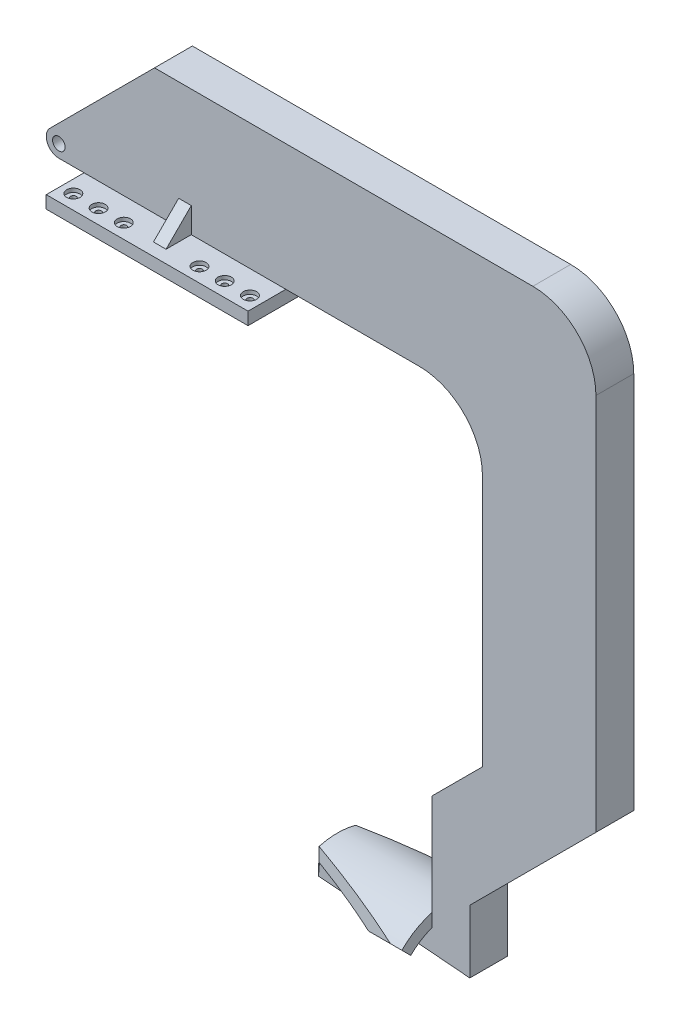
SolidWorks part; units mm, degrees
material "Stainless Steel (ferritic)"
ref_plane "Front Plane" through (0, 0, 0) normal (0, 0, 1) x (1, 0, 0)
ref_plane "Top Plane" through (0, 0, 0) normal (0, 1, 0) x (1, 0, 0)
ref_plane "Right Plane" through (0, 0, 0) normal (1, 0, 0) x (0, 0, -1)
sketch "Sketch1" plane through (0, 0, 0) normal (0, 0, 1) x (1, 0, 0)
  line L0 (-7.0711, 7.0711) -> (75.8579, 90)
  line L1 (75.8579, 90) -> (375.8579, 90)
  line L2 (425.8579, 40) -> (425.8579, -260)
  line L3 (425.8579, -260) -> (325.8579, -360)
  line L4 (325.8579, -360) -> (325.8579, -410)
  line L5 (325.8579, -410) -> (205.8579, -400)
  line L6 (205.8579, -400) -> (205.8579, -380)
  line L7 (205.8579, -380) -> (295.8579, -380)
  line L8 (295.8579, -380) -> (295.8579, -40) construction
  line L9 (285.8579, -10) -> (0, -10)
  line L10 (295.8579, -300) -> (335.8579, -260)
  line L11 (335.8579, -260) -> (335.8579, -60)
  line L12 (295.8579, -300) -> (295.8579, -380)
  arc A0 (295.8579, -40) -> (285.8579, -10) centre (245.8579, -40) ccw construction
  arc A1 (375.8579, 90) -> (425.8579, 40) centre (375.8579, 40) cw
  arc A2 (-7.0711, 7.0711) -> (0, -10) centre (0, 0) ccw
  circle A3 centre (0, 0) radius 5
  arc A4 (285.8579, -10) -> (335.8579, -60) centre (285.8579, -60) cw
  point P17 (325.8579, -260)
  point P18 (0, 0)
  point P19 (0, 0)
  point P24 (295.8579, -10)
  point P27 (425.8579, 90)
  dimension "D11" = 50
  dimension "D12" = 20
  dimension "D13" = 10
  dimension "D15" = 50
  dimension "D1" = 500
  dimension "D2" = 100
  dimension "D3" = 130
  dimension "D4" = 30
  dimension "D5" = 45
  dimension "D6" = 350
  dimension "D7" = 370
  dimension "D8" = 10
  dimension "D9" = 350
  dimension "D10" = 120
  dimension "D14" = 90
extrude "Boss-Extrude1" add sketch "Sketch1" along normal blind 30
sketch "Sketch2" plane through (0, -10, 0) normal (0, -1, 0) x (1, 0, 0)
  line L0 (0, 30) -> (0, 0) construction
  line L1 (20, -30) -> (180, -30)
  line L2 (20, -30) -> (20, 60)
  line L3 (20, 60) -> (180, 60)
  line L4 (180, -30) -> (180, 60)
  line L5 (0, 30) -> (0, 0)
  point P6 (0, 15)
  point P7 (20, 15)
  line M3 (0, 0) -> (285.8579, 0)
  line M5 (285.8579, 30) -> (0, 30)
  dimension "D1" = 160
  dimension "D2" = 90
  dimension "D3" = 20
extrude "Boss-Extrude2" add sketch "Sketch2" along normal blind 10 contours L4 L3 L2 M5 | L4 L2 M3 M5 | L1 L4 L2 M3 region at (100, -10, -15) region at (100, -10, 15) region at (100, -10, 45)
ref_plane "Plane2" through (100, 0, 0) normal (-1, 0, 0) x (0, 0, 1)
sketch "Sketch5" plane through (100, 0, 0) normal (-1, 0, 0) x (0, 0, 1)
  line L0 (30, 10) -> (50, -10)
  line L1 (30, -10) -> (30, 7.0711) construction
  line L2 (30, -10) -> (60, -10) construction
  line L3 (30, 90) -> (30, 7.0711) construction
  dimension "D1" = 10
  dimension "D2" = 20
rib "Rib1" sketch "Sketch5" sketch "Sketch5" thickness 10 extrusion direction parallel to sketch draft on no parameters "D1"=10
sketch "Sketch7" plane through (100, 0, 0) normal (-1, 0, 0) x (0, 0, 1)
  line L0 (0, 10) -> (-20, -10)
  line L1 (0, 90) -> (0, 7.0711) construction
  line L2 (-30, -10) -> (0, -10) construction
  dimension "D1" = 20
  dimension "D2" = 10
rib "Rib17" sketch "Sketch7" sketch "Sketch7" thickness 10 extrusion direction parallel to sketch draft on no parameters "D1"=10
sketch "Sketch8" plane through (0, -20, 0) normal (0, -1, 0) x (1, 0, 0)
  line L0 (20, 0) -> (95, 0) construction
  line L1 (105, 0) -> (180, 0) construction
  line L2 (105, 30) -> (180, 30) construction
  line L3 (20, 30) -> (95, 30) construction
  line L4 (20, 0) -> (95, 0)
  line L5 (105, 0) -> (180, 0)
  line L6 (105, 30) -> (180, 30)
  line L7 (20, 30) -> (95, 30)
  line L8 (180, 0) -> (180, 30) construction
  line L9 (180, 0) -> (180, 30)
  line L10 (40, 45) -> (40, -15) construction
  line L11 (20, 60) -> (20, 30) construction
  line L12 (40, 45) -> (75, 45) construction
  line L13 (125, 45) -> (160, 45) construction
  circle A0 centre (40, 45) radius 7.5
  circle A1 centre (75, 45) radius 7.5
  circle A2 centre (125, 45) radius 7.5
  circle A3 centre (160, 45) radius 7.5
  circle A4 centre (40, -15) radius 7.5
  circle A5 centre (75, -15) radius 7.5
  circle A6 centre (125, -15) radius 7.5
  circle A7 centre (160, -15) radius 7.5
  point P24 (180, 15)
  point P25 (40, 15)
  point P26 (57.5, 45)
  point P27 (20, 45)
  point P28 (57.5, 30)
  point P29 (142.5, 45)
  point P30 (142.5, 30)
  dimension "D1" = 15
  dimension "D2" = 35
  dimension "D3" = 35
extrude "Cut-Extrude1" [suppressed] cut sketch "Sketch8" against normal blind 10 contours A0 | A1 | A4 | A5 | A6 | A7 | A3 | A2
sketch "Sketch10" [suppressed] plane through (-31.6148, -379.3773, 0) normal (-0.083, -0.9965, 0) x (0.9965, -0.083, 0)
  line L4 (357.4542, 53.8909) -> (248.3304, 30)
  line L5 (357.4542, -23.8909) -> (248.3304, 0)
  line L9 (351.9262, 52.6806) -> (233.6057, 26.7763)
  line L10 (233.6057, 26.7763) -> (233.6057, 62.0562)
  line L11 (233.6057, 62.0562) -> (351.9262, 52.6806)
  line L15 (248.3304, 30) -> (368.7464, 30) construction
  line L16 (354.1513, -23.1678) -> (238.1443, 2.2301)
  line L17 (238.1443, 2.2301) -> (238.1443, -32.7213)
  line L18 (238.1443, -32.7213) -> (354.1513, -23.1678)
  line L19 (248.3304, 0) -> (368.7464, 0) construction
  ellipse E0 centre (360.6839, 15) end of major axis (360.6839, 70) minor radius 4.5675 (356.2896, 0) -> (357.4542, -23.8909) ccw construction
  ellipse E1 centre (360.6839, 15) end of major axis (360.6839, 70) minor radius 4.5675 (357.4542, 53.8909) -> (356.2896, 30) ccw construction
  ellipse E2 centre (360.6839, 15) end of major axis (360.6839, 70) minor radius 4.5675 (356.2896, 0) -> (357.4542, -23.8909) ccw
  ellipse E3 centre (360.6839, 15) end of major axis (360.6839, 70) minor radius 4.5675 (357.4542, 53.8909) -> (356.2896, 30) ccw
  dimension "D1" = 32.7213
  dimension "D2" = 116.007
  dimension "D3" = 35.2799
  dimension "D4" = 118.3205
  dimension "D5" = 32.0562
  dimension "D6" = 10.1861
extrude "Cut-Extrude3" [suppressed] cut sketch "Sketch10" against normal blind 30 contours L9 L10 L11 | L18 L16 L17
sketch "Sketch11" plane through (0, -10, 0) normal (0, 1, 0) x (1, 0, 0)
  point P0 (170, 16.5)
  point P1 (150, 16.5)
  point P3 (150, -48.5)
  point P5 (170, -48.5)
  point P7 (0, 0)
sketch "Sketch14" plane through (0, -10, 0) normal (0, 1, 0) x (1, 0, 0)
  point P0 (130, -48.5)
  point P1 (0, 0)
  dimension "D1" = 20
ref_plane "Plane3" through (100, 0, 0) normal (1, 0, 0) x (0, 0, -1)
hole_wizard "CBORE for M4 Hex Head Machine Screw2" positions "Sketch15" profile "Sketch16" counterbore size "M4" standard "ANSI Metric" end condition through all
sketch "Sketch15" plane through (0, -10, 0) normal (0, 1, 0) x (1, 0, 0)
  point P0 (130, -48.5)
  point P3 (150, -48.5)
  point P6 (170, -48.5)
sketch "Sketch16" plane through (130, -10, 48.5) normal (1, 0, 0) x (0, 0, 1)
  line L0 (0, 0) -> (0, 400)
  line L1 (0, 400) -> (2.25, 400)
  line L3 (2.25, 400) -> (2.25, 3)
  line L4 (2.25, 3) -> (5.295, 3)
  line L5 (5.295, 3) -> (5.295, 0)
  line L7 (5.295, 0) -> (0, 0)
  line L11 (0, -6.35) -> (0, 107.95) construction
  dimension "Thru Hole Dia." = 4.5
  dimension "Thru Hole Depth" = 400
  dimension "C'Bore Dia." = 10.59
  dimension "C'Bore Depth" = 3
mirror "Mirror1" about plane through (100, 0, 0) normal (1, 0, 0) of "CBORE for M4 Hex Head Machine Screw2"
ref_plane "Plane4" through (0, 0, 16) normal (0, 0, 1) x (1, 0, 0)
mirror "Mirror2" about plane through (0, 0, 16) normal (0, 0, 1) of "Mirror1", "CBORE for M4 Hex Head Machine Screw2"
sketch "Sketch19" plane through (295.8579, 0, 0) normal (-1, 0, 0) x (0, 0, 1)
  line L0 (-23.8909, -394.0242) -> (-16.8198, -401.0952)
  line L1 (46.8198, -401.0952) -> (53.8909, -394.0242)
  line L2 (15, -432.915) -> (15, -326.0199) construction
  line L3 (53.8909, -394.0242) -> (15, -432.915) construction
  line L4 (15, -432.915) -> (-23.8909, -394.0242) construction
  arc A0 (53.8909, -394.0242) -> (-23.8909, -394.0242) centre (15, -432.915) ccw
  arc A1 (46.8198, -401.0952) -> (-16.8198, -401.0952) centre (15, -432.915) ccw
  circle A2 centre (15, -432.915) radius 55 construction
  circle A3 centre (15, -432.915) radius 45 construction
  point P0 (27.6375, -427.5517)
  point P2 (-3.67, 79.8653)
  dimension "D1" = 110
  dimension "D3" = 90
  dimension "D2" = 10
extrude "Boss-Extrude5" add sketch "Sketch19" along normal up to surface (90 mm away) up to face at (205.8579, -390, 15)
sketch "Sketch20" plane through (-31.6837, -380.2049, 0) normal (-0.083, -0.9965, 0) x (0.9965, -0.083, 0)
  line L4 (346.4993, 62.2427) -> (238.365, 30)
  line L5 (344.1859, -32.1821) -> (238.365, 0)
  line L9 (346.4993, 62.2427) -> (228.1788, 26.9628)
  line L10 (228.1788, 26.9628) -> (228.1788, 62.2427)
  line L11 (228.1788, 62.2427) -> (346.4993, 62.2427)
  line L16 (344.1859, -32.1821) -> (228.1788, 3.0978)
  line L17 (228.1788, 3.0978) -> (228.1788, -32.1821)
  line L18 (228.1788, -32.1821) -> (344.1859, -32.1821)
  point P0 (248.3304, 30)
  point P2 (0, 0)
  point P3 (0, 0)
  point P4 (0, 0)
  point P5 (0, 0)
  point P7 (0, 0)
  point P13 (335.3455, 30)
  dimension "D2" = 116.007
  dimension "D3" = 35.2799
  dimension "D4" = 118.3205
  dimension "D6" = 10.1861
extrude "Cut-Extrude4" cut sketch "Sketch20" against normal blind 100 and the other way blind 100 contours L17 L18 L5 L16 | L11 L10 L9 L4 region at (235.0108, -402.4294, 50.4827) region at (234.2423, -402.3654, -20.4222)
